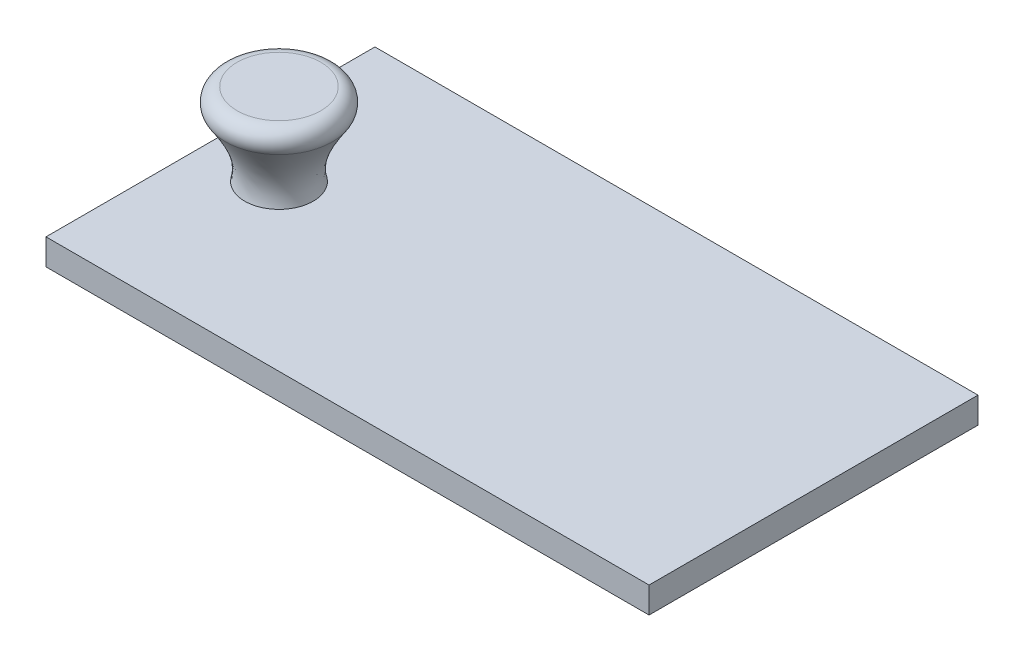
SolidWorks part; units mm, degrees
ref_plane "Front Plane" through (0, 0, 0) normal (0, 0, 1) x (1, 0, 0)
ref_plane "Top Plane" through (0, 0, 0) normal (0, 1, 0) x (1, 0, 0)
ref_plane "Right Plane" through (0, 0, 0) normal (1, 0, 0) x (0, 0, -1)
sketch "Sketch1" plane through (0, 0, 0) normal (0, 1, 0) x (1, 0, 0)
  line L1 (-22, -12) -> (22, -12)
  line L2 (-22, -12) -> (-22, 12)
  line L3 (-22, 12) -> (22, 12)
  line L4 (22, -12) -> (22, 12)
  line L5 (-22, -12) -> (22, 12) construction
  line L6 (-22, 12) -> (22, -12) construction
  point P0 (0, 0)
  dimension "D1" = 24
  dimension "D2" = 44
extrude "Boss-Extrude1" add sketch "Sketch1" along normal blind 1.9
sketch "Sketch2" plane through (0, 1.9, 0) normal (0, 1, 0) x (1, 0, 0)
  line L0 (-22, 12) -> (-22, -12) construction
  circle A0 centre (-17, 0) radius 2.5
  dimension "D1" = 5
ref_plane "Plane1" through (0, 7.9, 0) normal (0, 1, 0) x (1, 0, 0)
sketch "Sketch4" plane through (0, 7.9, 0) normal (0, 1, 0) x (1, 0, 0)
  circle A0 centre (-17, 0) radius 5
loft "Loft2" add profiles "Sketch4", "Sketch2" connector at (-13.9678, 7.9, 3.9757) connector at (-14.7383, 1.9, -1.0652)
fillet "Fillet1" radius 1 1 edges at (-17, 7.9, 5)
